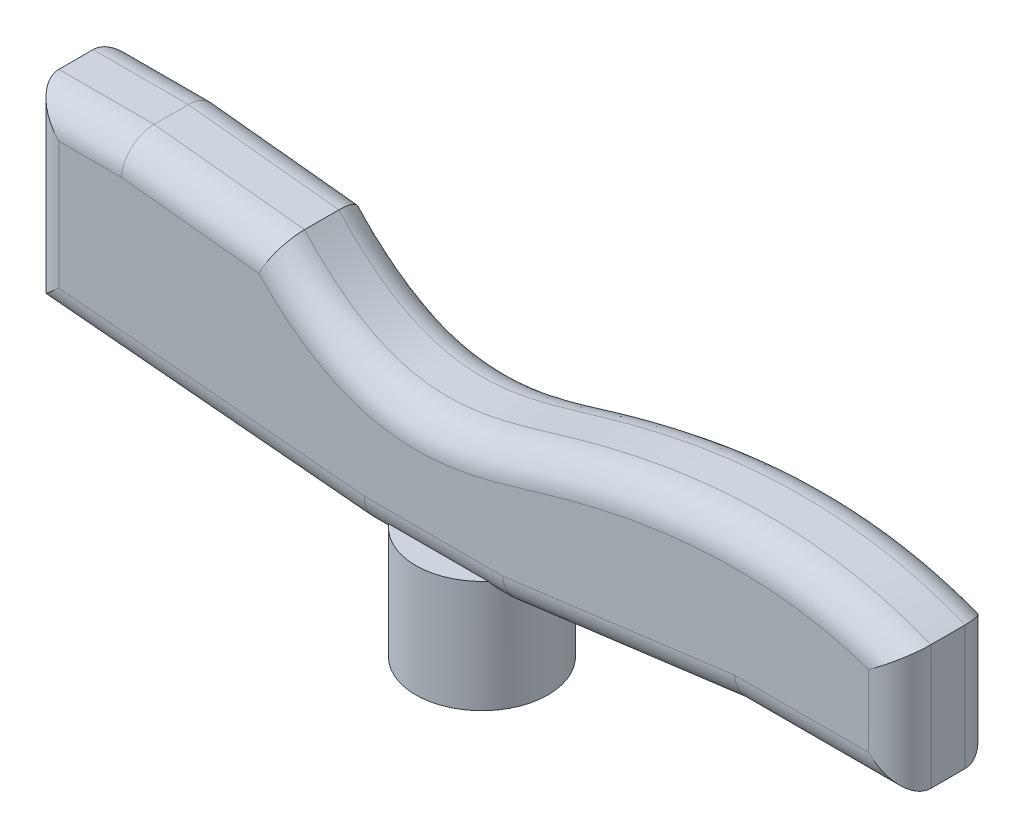
SolidWorks part; units mm, degrees
ref_plane "前基準面" through (0, 0, 0) normal (0, 0, 1) x (1, 0, 0)
ref_plane "上基準面" through (0, 0, 0) normal (0, 1, 0) x (1, 0, 0)
ref_plane "右基準面" through (0, 0, 0) normal (1, 0, 0) x (0, 0, -1)
sketch "草圖1" plane through (0, 0, 0) normal (0, 0, 1) x (1, 0, 0)
  line L0 (0, 0) -> (0, 60)
  line L1 (0, 60) -> (30.6281, 60)
  line L2 (30.6281, 60) -> (78.9616, 54.8725)
  line L3 (280.2175, 40) -> (280.2175, 0)
  line L4 (280.2175, 0) -> (227.8434, 0)
  line L5 (153.3118, -9.6901) -> (107.7898, -9.6901)
  spline S0 degree 3 poles (78.9616, 54.8725) (110.7562, 20.0434) (172.1725, 47.6811) (243.4018, 55.0032) (280.2175, 40) knots 0 0 0 0 0.434694 1 1 1 1
  spline S1 degree 1 poles (227.8434, 0) (153.3118, -9.6901) knots 0 0 1 1
  spline S2 degree 1 poles (107.7898, -9.6901) (0, 0) knots 0 0 1 1
  point P11 (30.6281, 50)
  point P13 (78.9616, 54.8725)
  point P14 (0, 0)
  point P15 (0, 0)
  point P16 (0, 0)
  dimension "D1" = 40
  dimension "D2" = 60
extrude "填料-伸長1" add sketch "草圖1" along normal blind 31
fillet "圓角3" radius 10 9 edges at (0, 30, 31) (15.3141, 60, 31) (54.7949, 57.4363, 31) (280.2175, 20, 31) (254.0304, 0, 31) (130.5508, -9.6901, 31)
fillet "圓角4" radius 10 9 edges at (130.5508, -9.6901, 0) (254.0304, 0, 0) (280.2175, 20, 0) (54.7949, 57.4363, 0) (15.3141, 60, 0) (0, 30, 0)
ref_plane "平面1" through (0, -11, 0) normal (0, 1, 0) x (1, 0, 0)
sketch "草圖4" plane through (0, -11, 0) normal (0, 1, 0) x (1, 0, 0)
  line L0 (-1000, -15.5) -> (49000, -15.5) construction
  line L1 (0, -21) -> (0, -10) construction
  line L2 (130.4514, -1000) -> (130.4514, 49000) construction
  line L3 (152.6645, 0) -> (108.2383, 0) construction
  circle A0 centre (130.4455, -15.5) radius 11.25
  point P5 (0, -15.5)
  point P10 (130.4514, 0)
  dimension "D1" = 22.5
extrude "伸長-薄件1" add sketch "草圖4" against normal blind 30 and the other way blind 6 thin thin type one direction wall 10
